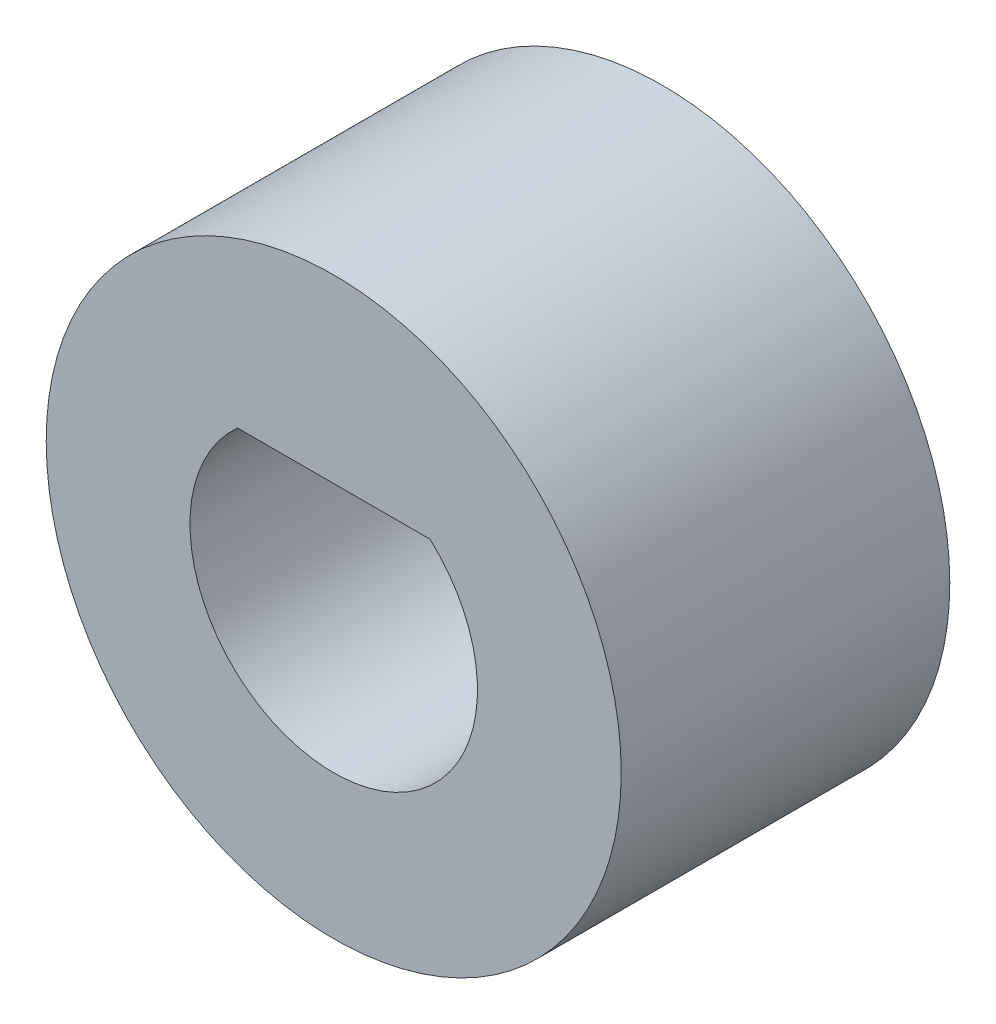
SolidWorks part; units mm, degrees
ref_plane "Plan de face" through (0, 0, 0) normal (0, 0, 1) x (1, 0, 0)
ref_plane "Plan de dessus" through (0, 0, 0) normal (0, 1, 0) x (1, 0, 0)
ref_plane "Plan de droite" through (0, 0, 0) normal (1, 0, 0) x (0, 0, -1)
sketch "Esquisse1" plane through (0, 0, 0) normal (0, 0, 1) x (1, 0, 0)
  line L0 (-2.3431, 2.6) -> (2.3431, 2.6)
  line L1 (-0.9885, -3.5) -> (1.037, -3.5) construction
  circle A0 centre (0, 0) radius 7
  arc A1 (-2.3431, 2.6) -> (2.3431, 2.6) centre (0, 0) ccw
  dimension "D1" = 14
  dimension "D2" = 7
  dimension "D3" = 6.1
extrude "Boss.-Extru.1" add sketch "Esquisse1" along normal blind 8
